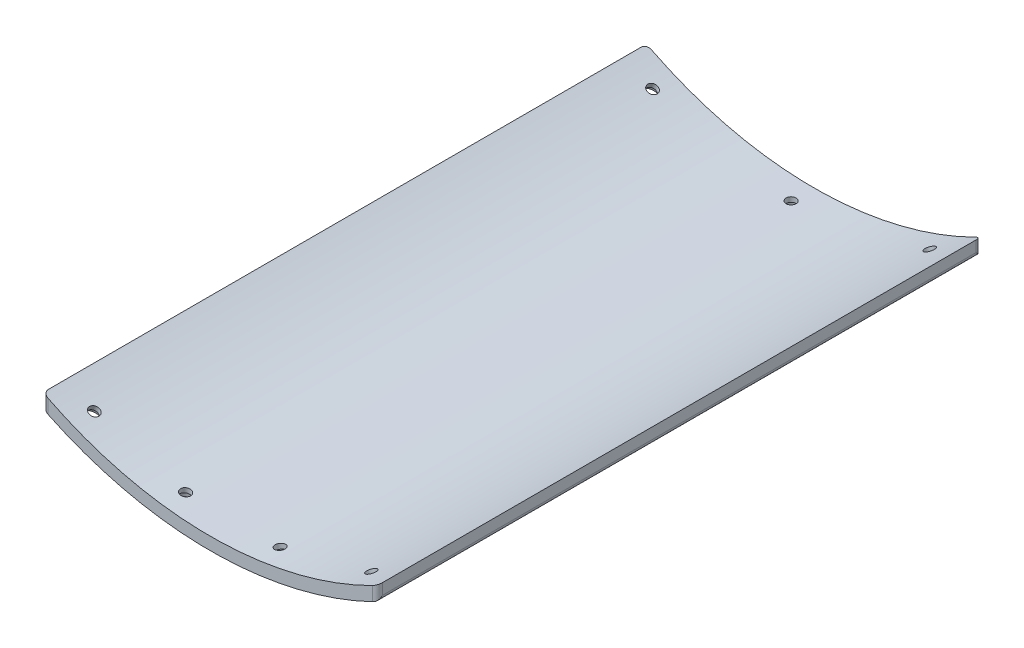
SolidWorks part; units mm, degrees
ref_plane "Front Plane" through (0, 0, 0) normal (0, 0, 1) x (1, 0, 0)
ref_plane "Top Plane" through (0, 0, 0) normal (0, 1, 0) x (1, 0, 0)
ref_plane "Right Plane" through (0, 0, 0) normal (1, 0, 0) x (0, 0, -1)
sketch "Sketch1" plane through (0, 0, 0) normal (0, 0, 1) x (1, 0, 0)
  line L0 (0, 0) -> (0, -144) construction
  line L1 (-66.4918, -127.7296) -> (-66.4918, -133.3411)
  line L2 (66.4918, -127.7296) -> (66.4918, -133.3411)
  line L3 (0, 0) -> (-66.4918, -127.7296) construction
  line L5 (0, 0) -> (66.4918, -127.7296) construction
  arc A0 (-66.4918, -127.7296) -> (66.4918, -127.7296) centre (0, 0) ccw
  arc A1 (-66.4918, -133.3411) -> (66.4918, -133.3411) centre (0, 0) ccw
  dimension "D1" = 144
  dimension "D4" = 149
  dimension "D2" = 27.5
  dimension "D3" = 27.5
extrude "Boss-Extrude1" add sketch "Sketch1" along normal blind 120 and the other way blind 120
fillet "Fillet1" radius 2 6 edges at (-66.4918, -130.5353, -120) (66.4918, -130.5353, -120) (66.4918, -130.5353, 120) (-66.4918, -130.5353, 120) (-66.4918, -133.3411, 0) (66.4918, -133.3411, 0)
hole_wizard "Hole1" positions "3DSketch1" profile "Sketch2" legacy end condition through all
sketch3d "3DSketch1"
  line L1 (0, 0, -111) -> (0, 0, 111) construction
  line L3 (0, 0, 111) -> (-57.0198, -137.6581, 111) construction
  line L6 (0, 0, 111) -> (-19.4484, -147.7253, 111) construction
  line L9 (0, 0, 111) -> (19.4484, -147.7253, 111) construction
  line L12 (0, 0, 111) -> (57.0198, -137.6581, 111) construction
  line L14 (0, 0, 111) -> (0, -149, 111) construction
  line L16 (0, 0, -111) -> (57.0198, -137.6581, -111) construction
  line L23 (0, 0, -111) -> (0, -149, -111) construction
  line L26 (0, 0, -111) -> (-57.0198, -137.6581, -111) construction
  point P0 (-57.0198, -137.6581, 111)
  point P3 (-19.4484, -147.7253, 111)
  point P6 (19.4484, -147.7253, 111)
  point P9 (-57.0198, -137.6581, -111)
  point P12 (0, -149, -111)
  point P15 (57.0198, -137.6581, -111)
  point P18 (57.0198, -137.6581, 111)
  point P76 (0, 0, 0)
  dimension "D1" = 111
  dimension "D2" = 7.5
  dimension "D3" = 7.5
  dimension "D4" = 15
  dimension "D5" = 15
  dimension "D6" = 22.5
  dimension "D7" = 22.5
sketch "Sketch2" plane through (-57.0198, -137.6581, 111) normal (0, 0, 1) x (0.9239, -0.3827, 0)
  line L0 (0, 0) -> (0, 56.5786)
  line L1 (0, 56.5786) -> (2, 56.5786)
  line L3 (2, 56.5786) -> (2, 3.1)
  line L4 (2, 3.1) -> (4, 3.1)
  line L5 (4, 3.1) -> (4, 0)
  line L7 (4, 0) -> (0, 0)
  line L11 (0, -6.35) -> (0, 107.95) construction
  dimension "Thru Hole Dia." = 4
  dimension "Thru Hole Depth" = 56.5786
  dimension "C'Bore Dia." = 8
  dimension "C'Bore Depth" = 3.1
